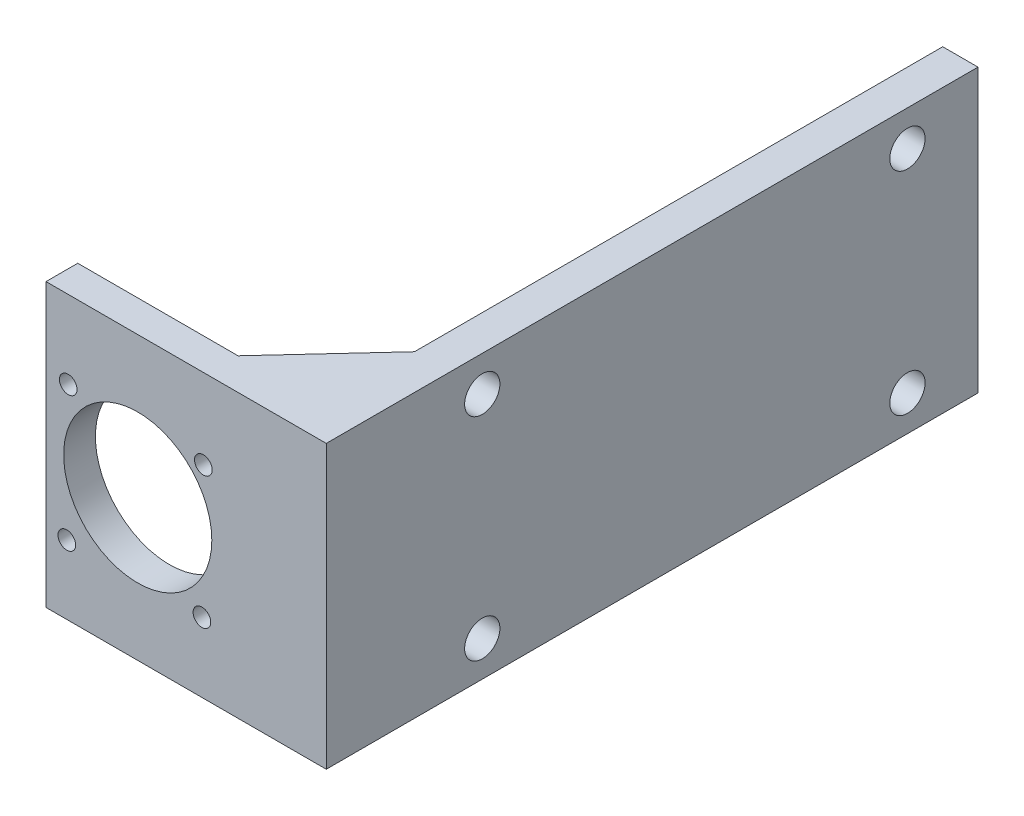
SolidWorks part; units mm, degrees
ref_plane "Front Plane" through (0, 0, 0) normal (0, 0, 1) x (1, 0, 0)
ref_plane "Top Plane" through (0, 0, 0) normal (0, 1, 0) x (1, 0, 0)
ref_plane "Right Plane" through (0, 0, 0) normal (1, 0, 0) x (0, 0, -1)
sketch "Sketch1" plane through (0, 0, 0) normal (0, 0, 1) x (1, 0, 0)
  line L0 (-26, 0) -> (0, 0) construction
  line L1 (-26, -6) -> (0, -6)
  line L2 (-26, -6) -> (-26, 34)
  line L3 (-26, 34) -> (0, 34)
  line L5 (-26, 28) -> (0, 28) construction
  line L6 (0, 34) -> (13.72, 34)
  line L7 (13.72, -36) -> (13.72, 64) construction
  line L8 (0, -6) -> (13.72, -6)
  line L9 (13.72, -6) -> (13.72, 34)
  circle A0 centre (-13, 14) radius 10.5
  circle A1 centre (-3.9, 3.85) radius 1.25
  circle A2 centre (-23.05, 3.75) radius 1.25
  circle A3 centre (-22.85, 22.95) radius 1.25
  circle A4 centre (-3.7, 22.65) radius 1.25
  dimension "D3" = 21
  dimension "D1" = 6
  dimension "D2" = 6
extrude "Boss-Extrude1" add sketch "Sketch1" along normal blind 4.5
sketch "Sketch2" plane through (0, 0, 0) normal (0, 0, -1) x (-1, 0, 0)
  line L0 (26, -6) -> (-13.72, -6) construction
  line L1 (-13.72, 34) -> (-8.72, 34)
  line L2 (-13.72, 34) -> (-13.72, -6)
  line L3 (-13.72, -6) -> (-8.72, -6)
  line L4 (-8.72, 34) -> (-8.72, -6)
  dimension "D1" = 5
extrude "Boss-Extrude2" add sketch "Sketch2" along normal up to surface (87.8698 mm away) up to face at (-6.14, 34, 2.25)
sketch "Sketch3" plane through (8.72, 0, 0) normal (-1, 0, 0) x (0, 0, 1)
  circle A0 centre (-77.8698, 29) radius 2.5
  circle A1 centre (-77.8698, -1) radius 2.5
  circle A2 centre (-17.6098, -1) radius 2.5
  circle A3 centre (-17.6098, 29) radius 2.5
extrude "Cut-Extrude1" cut sketch "Sketch3" against normal through all
ref_plane "Plane1" through (0, 14, 0) normal (0, 1, 0) x (1, 0, 0)
sketch "Sketch4" plane through (0, 14, 0) normal (0, 1, 0) x (1, 0, 0)
  line L0 (8.72, 13) -> (-3.28, 0)
  line L1 (8.72, 87.8698) -> (8.72, 0) construction
  line L2 (8.72, 0) -> (-26, 0) construction
  line L3 (-3.28, 0) -> (8.72, 0)
  line L4 (8.72, 0) -> (8.72, 13)
  dimension "D1" = 12
  dimension "D2" = 13
extrude "Boss-Extrude3" add sketch "Sketch4" along normal mid plane 40
sketch "Sketch5" plane through (0, 0, 0) normal (0, 0, -1) x (-1, 0, 0)
  line L12 (-8.72, 34) -> (-8.72, -6) construction
  line L17 (-8.72, -3) -> (3.28, -3)
  line L18 (-8.72, -3) -> (-8.72, 31)
  line L19 (-8.72, 31) -> (3.28, 31)
  line L20 (3.28, -3) -> (3.28, 31)
  line L21 (3.28, 34) -> (3.28, 23.8273) construction
  line L22 (-8.72, -6) -> (3.28, -6) construction
  line L23 (-8.72, 34) -> (3.28, 34) construction
  dimension "D1" = 3
  dimension "D2" = 3
extrude "Cut-Extrude2" cut sketch "Sketch5" along normal up to vertex (13 mm away) up to point (8.72, -6, -13)
fillet "Fillet1" radius 5 1 edges at (8.72, 14, 0)
